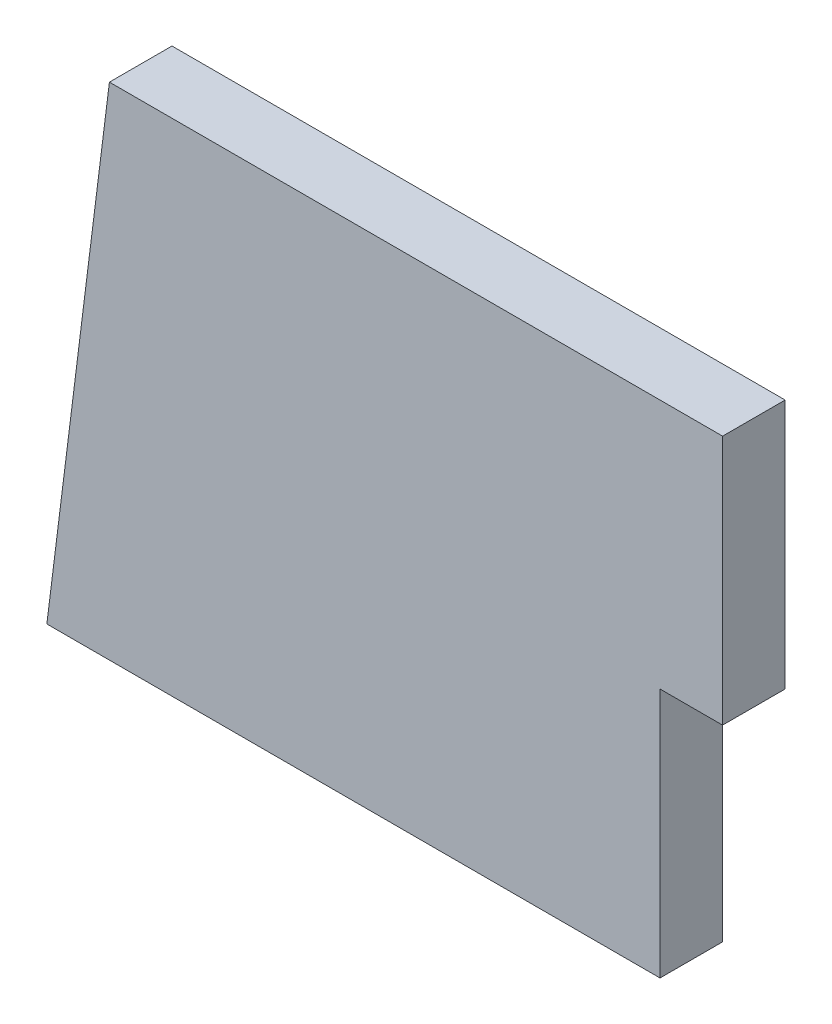
SolidWorks part; units mm, degrees
ref_plane "Plan de face" through (0, 0, 0) normal (0, 0, 1) x (1, 0, 0)
ref_plane "Plan de dessus" through (0, 0, 0) normal (0, 1, 0) x (1, 0, 0)
ref_plane "Plan de droite" through (0, 0, 0) normal (1, 0, 0) x (0, 0, -1)
sketch "Esquisse1" plane through (0, 0, 0) normal (0, 0, 1) x (1, 0, 0)
  line L0 (0, 0) -> (0, -20)
  line L1 (0, -20) -> (-5, -20)
  line L2 (-5, -20) -> (-5, -40)
  line L3 (-5, -40) -> (-54, -40)
  line L4 (-54, -40) -> (-49, 0)
  line L5 (-49, 0) -> (0, 0)
  dimension "D1" = 20
  dimension "D2" = 5
  dimension "D3" = 49
extrude "Boss.-Extru.1" add sketch "Esquisse1" along normal blind 5
